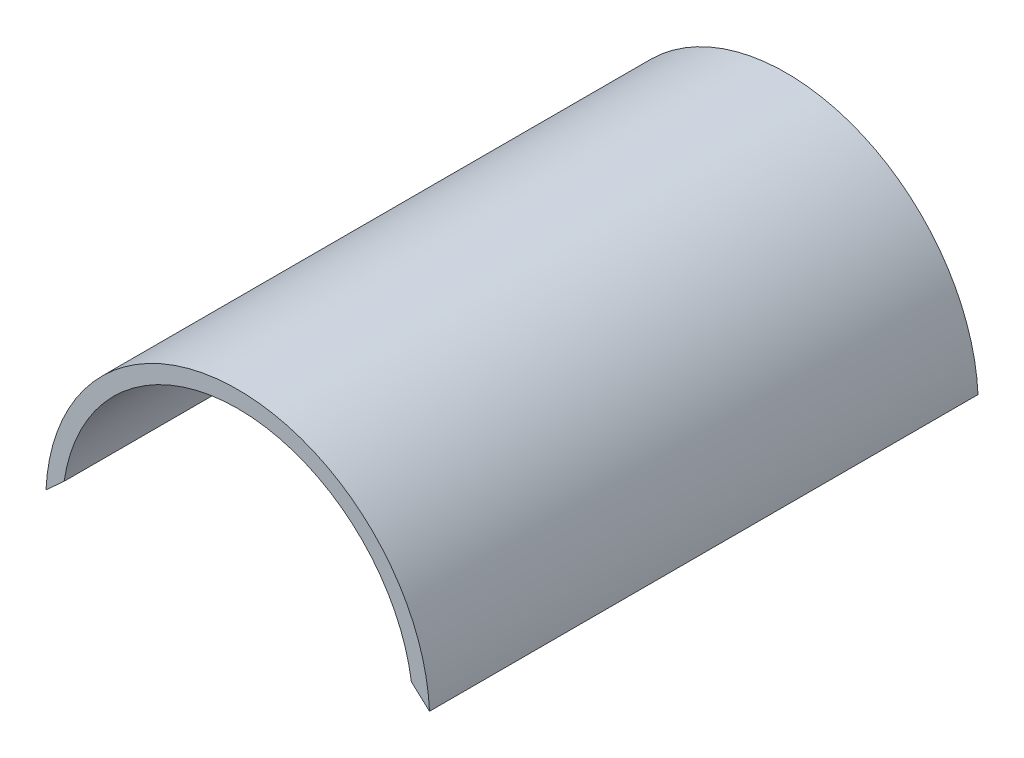
SolidWorks part; units mm, degrees
ref_plane "Front Plane" through (0, 0, 0) normal (0, 0, 1) x (1, 0, 0)
ref_plane "Top Plane" through (0, 0, 0) normal (0, 1, 0) x (1, 0, 0)
ref_plane "Right Plane" through (0, 0, 0) normal (1, 0, 0) x (0, 0, -1)
sketch "Sketch1" plane through (0, 0, 0) normal (0, 0, 1) x (1, 0, 0)
  line L0 (0, 0) -> (0, 44.45) construction
  line L1 (-40.2039, 5.9378) -> (40.2039, 5.9378) construction
  line L2 (-44.399, 2.1278) -> (44.399, 2.1278) construction
  line L3 (-40.2039, 5.9378) -> (-44.399, 2.1278)
  line L4 (40.2039, 5.9378) -> (44.399, 2.1278)
  arc A0 (44.399, 2.1278) -> (-44.399, 2.1278) centre (0, 0) ccw
  arc A1 (40.2039, 5.9378) -> (-40.2039, 5.9378) centre (0, 0) ccw
  dimension "D1" = 88.9
  dimension "D2" = 3.81
  dimension "D3" = 3.81
extrude "Boss-Extrude1" add sketch "Sketch1" along normal blind 127
